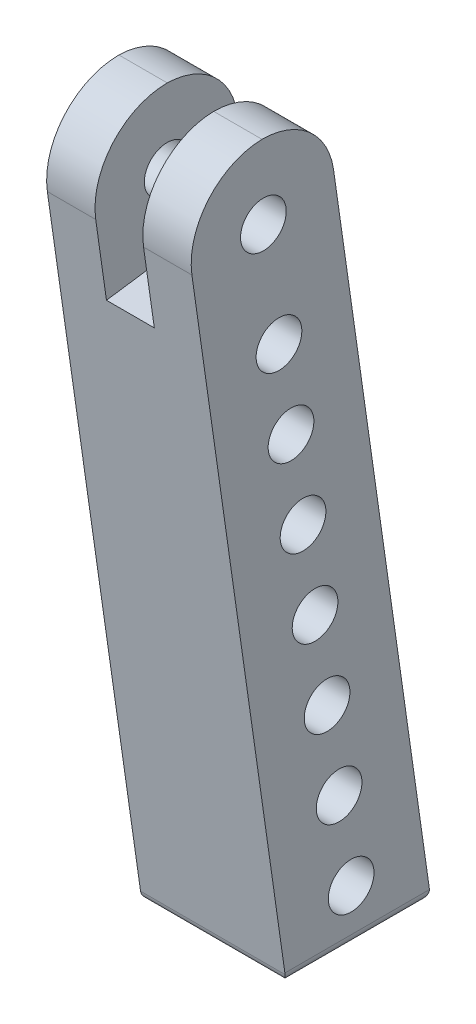
SolidWorks part; units mm, degrees
material "ABS"
ref_plane "Front" through (0, 0, 0) normal (0, 0, 1) x (1, 0, 0)
ref_plane "Top" through (0, 0, 0) normal (0, 1, 0) x (1, 0, 0)
ref_plane "Right" through (0, 0, 0) normal (1, 0, 0) x (0, 0, -1)
sketch "草图1" plane through (0, 0, 0) normal (0, 1, 0) x (1, 0, 0)
  line L1 (-6.8, -6.8) -> (6.8, -6.8)
  line L2 (-6.8, -6.8) -> (-6.8, 6.8)
  line L3 (-6.8, 6.8) -> (6.8, 6.8)
  line L4 (6.8, -6.8) -> (6.8, 6.8)
  line L5 (-6.8, -6.8) -> (6.8, 6.8) construction
  line L6 (-6.8, 6.8) -> (6.8, -6.8) construction
  point P0 (0, 0)
  dimension "D1" = 13.6
  dimension "D2" = 13.6
ref_plane "基准面1" through (0, 70, 0) normal (0, 1, 0) x (1, 0, 0)
sketch "草图2" plane through (0, 70, 0) normal (0, 1, 0) x (1, 0, 0)
  line L1 (-6.8, -16.8) -> (6.8, -16.8)
  line L2 (-6.8, -16.8) -> (-6.8, -3.2)
  line L3 (-6.8, -3.2) -> (6.8, -3.2)
  line L4 (6.8, -16.8) -> (6.8, -3.2)
  line L5 (-6.8, -16.8) -> (6.8, -3.2) construction
  line L6 (-6.8, -3.2) -> (6.8, -16.8) construction
  point P0 (0, -10)
  dimension "D1" = 13.6
  dimension "D2" = 13.6
  dimension "D3" = 10
sketch "草图3" plane through (0, 0, 0) normal (1, 0, 0) x (0, 0, -1)
  line L0 (-13.4, 70) -> (-3.4, 0) construction
  line L1 (-16.8, 70) -> (-3.2, 70) construction
  line L2 (-3.2, 70) -> (-16.8, 70) construction
  line L3 (-6.8, 0) -> (6.8, 0) construction
loft "放样1" add profiles "草图2", "草图1" connector at (-6.8, 70, 16.8) connector at (-6.8, 0, 6.8)
sketch "草图6" plane through (0, -0.952, 6.664) normal (0, -0.1414, 0.9899) x (1, 0, 0)
  line L0 (0, 71.1915) -> (0, 0.4808) construction
  line L1 (-6.8, 71.6723) -> (6.8, 71.6723) construction
  line L2 (-2.25, 71.6723) -> (2.25, 71.6723)
  line L3 (-2.25, 71.6723) -> (-2.25, 56.6723)
  line L4 (-2.25, 56.6723) -> (2.25, 56.6723)
  line L5 (2.25, 71.6723) -> (2.25, 56.6723)
  line L6 (-2.25, 71.6723) -> (2.25, 56.6723) construction
  line L7 (-2.25, 56.6723) -> (2.25, 71.6723) construction
  point P2 (0, 64.1723)
  dimension "D1" = 15
  dimension "D2" = 4.5
extrude "切除-拉伸3" cut sketch "草图6" against normal through all both and the other way through all
fillet "圆角1" radius 6.8 2 edges
sketch "草图4" plane through (6.8, 0, 0) normal (1, 0, 0) x (0, 0, -1)
  line L0 (-6.8, 0) -> (6.8, 0) construction
  line L1 (0, 0) -> (-9.9637, 70) construction
  line L2 (50, 70) -> (-50, 70) construction
  circle A0 centre (-8.9673, 63) radius 2.15
  dimension "D1" = 4.3
  dimension "D2" = 7
extrude "切除-拉伸1" cut sketch "草图4" against normal through all
sketch "草图5" plane through (6.8, 0, 0) normal (1, 0, 0) x (0, 0, -1)
  line L0 (-8.9673, 63) -> (0, 0) construction
  line L1 (-6.8, 0) -> (6.8, 0) construction
  circle A0 centre (-0.7117, 5) radius 2.15
  dimension "D1" = 4.3
  dimension "D2" = 5
extrude "切除-拉伸2" cut sketch "草图5" against normal through all
pattern_linear "阵列(线性)1" count 7 spacing 8 along (0, 0.9899, 0.1414) of "切除-拉伸2"
fillet "圆角2" radius 6.8 2 edges
fillet "圆角3" radius 1 3 edges
